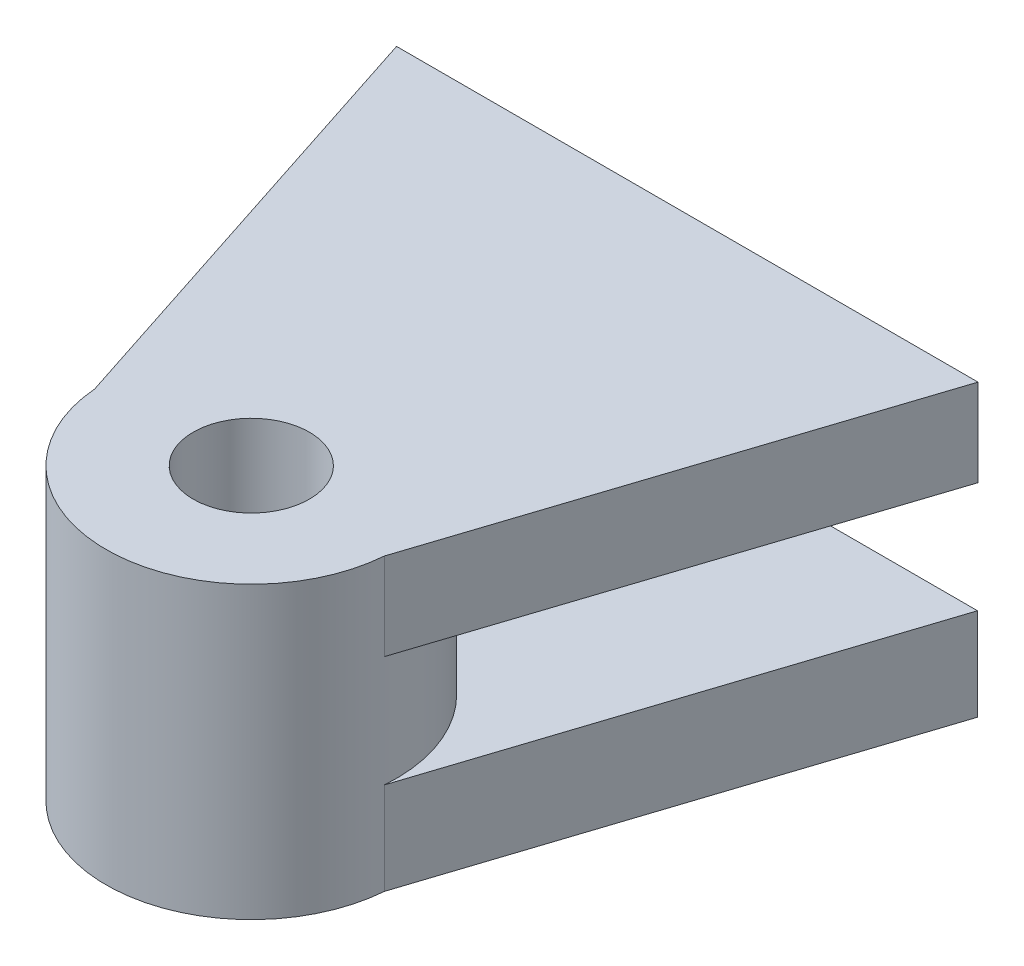
SolidWorks part; units mm, degrees
ref_plane "Front Plane" through (0, 0, 0) normal (0, 0, 1) x (1, 0, 0)
ref_plane "Top Plane" through (0, 0, 0) normal (0, 1, 0) x (1, 0, 0)
ref_plane "Right Plane" through (0, 0, 0) normal (1, 0, 0) x (0, 0, -1)
sketch "Sketch1" plane through (0, 0, 0) normal (0, 1, 0) x (1, 0, 0)
  line L0 (0, 0) -> (40, 0)
  line L4 (0, 0) -> (10.0326, -30.8063)
  line L5 (29.9674, -30.8063) -> (40, 0)
  line L6 (20, 0) -> (20, -17.1488) construction
  line L7 (10.0326, -30.8063) -> (29.9674, -30.8063) construction
  circle A0 centre (20, -30) radius 4
  circle A1 centre (20, -30) radius 10
  dimension "D2" = 20
  dimension "D3" = 8
  dimension "D1" = 40
  dimension "D4" = 30
extrude "Boss-Extrude1" add sketch "Sketch1" along normal blind 6.35 contours A1 L5 L0 L4 | A1 | A0 region at (20, 0, 10.7969)
extrude "Boss-Extrude2" add sketch "Sketch1<3>" along normal blind 20 contours A1 A0 region at (19.6079, 0, 20.2908)
sketch "Sketch1<3>" plane through (0, 0, 0) normal (0, 1, 0) x (1, 0, 0) same geometry as "Sketch1"
ref_plane "Plane1" through (0, 10, 0) normal (0, 1, 0) x (1, 0, 0)
sketch "Sketch2" plane through (0, 20, 0) normal (0, 1, 0) x (1, 0, 0)
  line L0 (0, 0) -> (40.0342, 0)
  line L1 (0, 0) -> (40, 0) construction
  line L2 (40.0342, 0) -> (29.9674, -30.8063)
  line L3 (29.9674, -30.8063) -> (40, 0) construction
  line L4 (0, 0) -> (10.0326, -30.8063)
  line L5 (0, 0) -> (10.0326, -30.8063) construction
  circle A0 centre (20, -30) radius 10 construction
  circle A1 centre (20, -30) radius 10
  circle A2 centre (20, -30) radius 4
  point P17 (40.0342, 0)
  circle M1 centre (20, -30) radius 4
  circle M2 centre (20, -30) radius 10
extrude "Boss-Extrude3" add sketch "Sketch2" against normal blind 6 contours L0 L4 L2 M2 | M2 M1 region at (20.0117, 20, 10.7965) region at (19.6079, 20, 20.2908)
equation "\"20.00mm_5\"=20"
